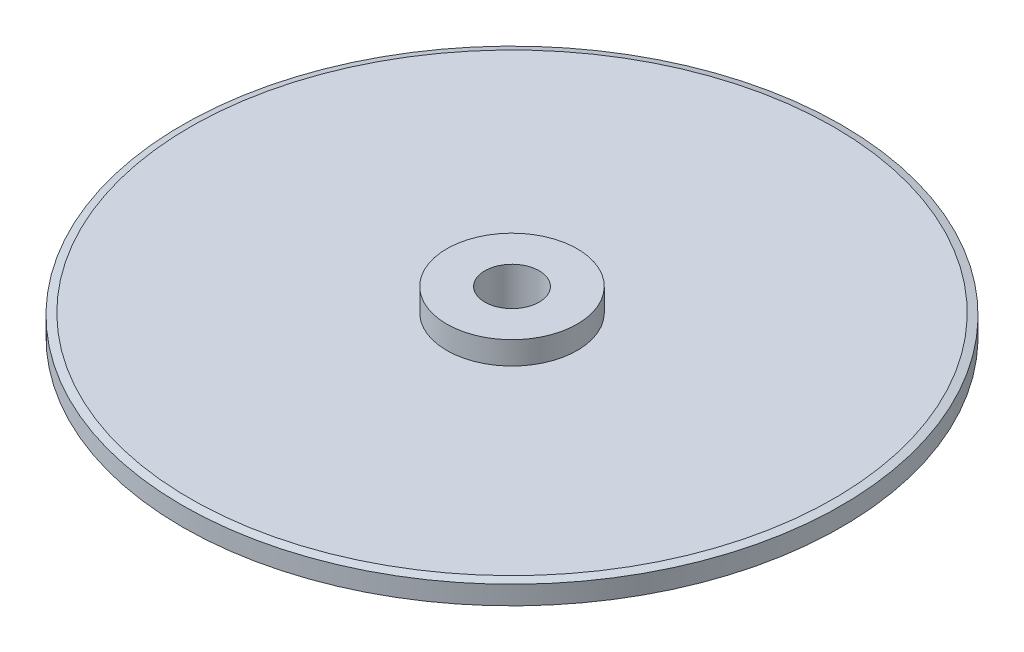
SolidWorks part; units mm, degrees
material "Сталь ШХ15 ГОСТ 801-78"
ref_plane "Plane1" through (0, 0, 0) normal (0, 0, 1) x (1, 0, 0)
ref_plane "Plane2" through (0, 0, 0) normal (0, 1, 0) x (1, 0, 0)
ref_plane "Plane3" through (0, 0, 0) normal (1, 0, 0) x (0, 0, -1)
sketch "Эскиз1" plane through (0, 0, 0) normal (0, 0, 1) x (1, 0, 0)
  line L0 (0, 0) -> (60.6, 0)
  line L1 (60.6, 0) -> (60.6, 4.2)
  line L2 (60.6, 4.2) -> (12, 4.2)
  line L3 (12, 4.2) -> (12, 8.4)
  line L4 (12, 8.4) -> (0, 8.4)
  line L5 (0, 8.4) -> (0, 0)
  dimension "D1" = 4.2
  dimension "30" = 60.6
  dimension "D3" = 12
  dimension "D4" = 4.2
ref_axis "Ось1" through (0, 8.4, 0) along (0, -1, 0)
revolve "Повернуть2" add sketch "Эскиз1" angle 360 about axis through (0, 8.4, 0) along (0, -1, 0)
chamfer "Фаска1" distance 1.41 angle 15 1 edges at (0, 4.2, 60.6) first distance on face at (0, 4.2, 12)
chamfer "Фаска2" distance 1.41 angle 15 1 edges at (0, 0, 60.6) first distance on face at (0, 0, 60.6)
sketch "Эскиз2" plane through (0, 0, 0) normal (0, -1, 0) x (-1, 0, 0)
  circle A0 centre (0, 0) radius 5
  dimension "D1" = 10
sketch "Эскиз3" plane through (0, 0, 0) normal (0, 0, 1) x (1, 0, 0)
  circle A0 centre (0, 5.828) radius 1
extrude "Вырез-Вытянуть3" cut sketch "Эскиз2" against normal through all both contours A0
